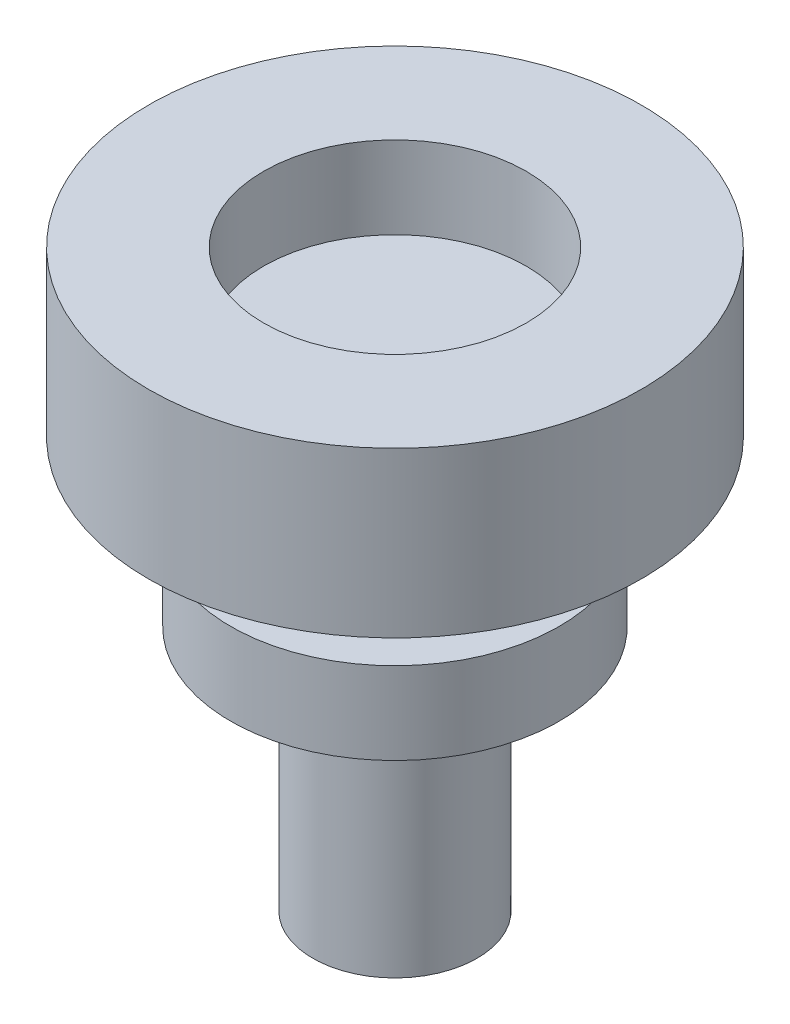
SolidWorks part; units mm, degrees
ref_plane "Front Plane" through (0, 0, 0) normal (0, 0, 1) x (1, 0, 0)
ref_plane "Top Plane" through (0, 0, 0) normal (0, 1, 0) x (1, 0, 0)
ref_plane "Right Plane" through (0, 0, 0) normal (1, 0, 0) x (0, 0, -1)
sketch "Sketch1" plane through (0, 0, 0) normal (0, 1, 0) x (1, 0, 0)
  circle A0 centre (-0.522, 0.5111) radius 1.6
  circle A1 centre (-0.522, 0.5111) radius 3
  dimension "D1" = 3.2
  dimension "D2" = 6
extrude "Boss-Extrude1" add sketch "Sketch1" along normal blind 2
extrude "Boss-Extrude2" add sketch "Sketch1<3>" along normal blind 1 contours A0 region at (-0.522, 0, -0.5111)
sketch "Sketch1<3>" plane through (0, 0, 0) normal (0, 1, 0) x (1, 0, 0) same geometry as "Sketch1"
sketch "Sketch5" plane through (0, 0, 0) normal (0, -1, 0) x (1, 0, 0)
  circle A2 centre (-0.522, -0.5111) radius 1.5
  circle A3 centre (-0.522, -0.5111) radius 1.5
  dimension "D2" = 3
  dimension "D1" = 1.5
extrude "Boss-Extrude3" add sketch "Sketch5" along normal blind 1 contours A3
sketch "Sketch6" plane through (0, -1, 0) normal (0, -1, 0) x (1, 0, 0)
  circle A0 centre (-0.522, -0.5111) radius 2
  dimension "D1" = 4
extrude "Boss-Extrude4" add sketch "Sketch6" along normal blind 1
sketch "Sketch8" plane through (0, -2, 0) normal (0, -1, 0) x (-1, 0, 0)
  circle A0 centre (0.522, 0.5111) radius 1
extrude "Boss-Extrude5" add sketch "Sketch8" along normal blind 3 contours A0
